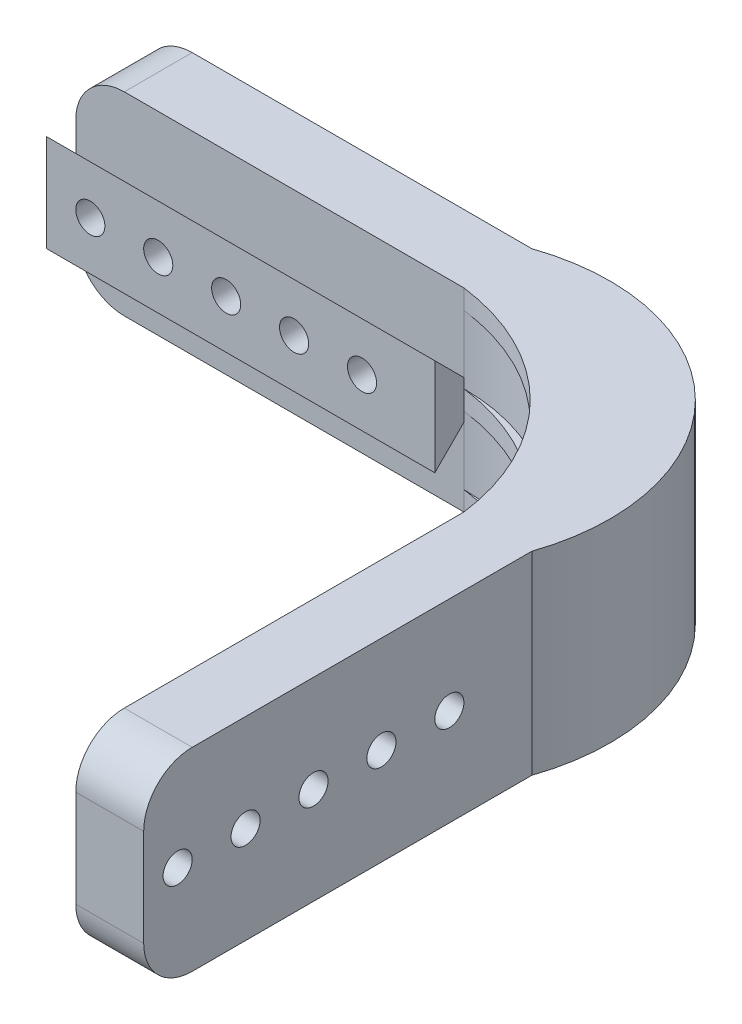
SolidWorks part; units mm, degrees
ref_plane "Front Plane" through (0, 0, 0) normal (0, 0, 1) x (1, 0, 0)
ref_plane "Top Plane" through (0, 0, 0) normal (0, 1, 0) x (1, 0, 0)
ref_plane "Right Plane" through (0, 0, 0) normal (1, 0, 0) x (0, 0, -1)
sketch "Sketch1" plane through (0, 0, 0) normal (0, 1, 0) x (1, 0, 0)
  line L0 (0, 0) -> (40, 0)
  line L1 (67, -27) -> (67, -67)
  line L2 (0, -7) -> (40, -7)
  line L3 (60, -27) -> (60, -67)
  line L4 (60, -67) -> (67, -67)
  line L5 (0, -7) -> (0, 0)
  arc A0 (40, 0) -> (67, -27) centre (40, -27) cw
  arc A1 (40, -7) -> (60, -27) centre (40, -27) cw
  dimension "D4" = 20
  dimension "D2" = 40
  dimension "D3" = 40
  dimension "D1" = 7
extrude "Boss-Extrude1" add sketch "Sketch1" along normal blind 20
sketch "Sketch2" plane through (0, 0, 0) normal (1, 0, 0) x (0, 0, -1)
  line L1 (-7, 20) -> (-7, 0) construction
  line L2 (-10, 15) -> (-10, 5)
  line L3 (-10, 5) -> (-7, 8)
  line L4 (-7, 8) -> (-7, 12)
  line L5 (-7, 10) -> (-10, 10) construction
  line L6 (-7, 12) -> (-10, 15)
  line L7 (-7, 20) -> (-27, 20) construction
  dimension "D1" = 10
  dimension "D2" = 4
  dimension "D3" = 3
  dimension "D9" = 10
extrude "Boss-Extrude2" add sketch "Sketch2" along normal blind 40
ref_plane "Plane1" through (0, 0, 65) normal (0, 0, 1) x (1, 0, 0)
sketch "Sketch3" plane through (0, 0, 65) normal (0, 0, 1) x (1, 0, 0)
  line L6 (67, 12) -> (67, 8)
  line L8 (67, 20) -> (67, 0) construction
  line L9 (67, 8) -> (70, 5)
  line L10 (70, 5) -> (70, 15)
  line L11 (70, 15) -> (67, 12)
  line L12 (67, 10) -> (70, 10) construction
  line L13 (60, 20) -> (67, 20) construction
  dimension "D1" = 10
  dimension "D2" = 4
  dimension "D3" = 3
  dimension "D4" = 10
extrude "Boss-Extrude3" [suppressed] add sketch "Sketch3" against normal blind 40
sketch "Sketch4" plane through (0, 0, 0) normal (1, 0, 0) x (0, 0, -1)
  line L0 (-27, 20) -> (-67, 20) construction
  line L1 (-67, 20) -> (-67, 0) construction
  circle A0 centre (-63.5, 10) radius 1.5
  dimension "D1" = 3
  dimension "D2" = 10
  dimension "D3" = 3.5
extrude "Cut-Extrude1" cut sketch "Sketch4" along normal blind 75
pattern_linear "LPattern1" count 5 spacing 7 along (0, 0, -1) of "Cut-Extrude1"
sketch "Sketch5" plane through (0, 0, 0) normal (0, 0, 1) x (1, 0, 0)
  line L0 (40, 20) -> (0, 20) construction
  line L1 (0, 20) -> (0, 0) construction
  circle A0 centre (4.5, 10) radius 1.5
  dimension "D1" = 3
  dimension "D2" = 10
  dimension "D3" = 4.5
extrude "Cut-Extrude2" cut sketch "Sketch5" along normal blind 14
pattern_linear "LPattern2" count 5 spacing 7 along (1, 0, 0) of "Cut-Extrude2"
fillet "Fillet1" [suppressed] radius 0.5
fillet "Fillet2" radius 5 4 edges at (63.5, 0, 67) (63.5, 20, 67) (0, 0, 3.5) (0, 20, 3.5)
sketch "Sketch6" plane through (0, 0, 0) normal (0, 1, 0) x (1, 0, 0)
  line L6 (60, -27) -> (60, -62)
  line L7 (60, -62) -> (67, -62)
  line L8 (67, -62) -> (67, -27)
  line L9 (40, 0) -> (5, 0)
  line L10 (5, 0) -> (5, -7)
  line L11 (5, -7) -> (40, -7)
  arc A0 (67, -27) -> (40, 0) centre (46.8968, -20.1032) ccw
  arc A3 (67, -27) -> (40, 0) centre (40, -27) ccw
  arc A4 (60, -27) -> (40, -7) centre (40, -27) ccw
  arc A5 (67, -27) -> (40, 0) centre (40, -27) ccw
  dimension "D1" = 0
extrude "Boss-Extrude4" add sketch "Sketch6" along normal up to surface (20 mm away) up to face at (44.2168, 20, 22.7832)
sketch "Sketch8" plane through (0, 0, 0) normal (0, 1, 0) x (1, 0, 0)
  arc A0 (40, -7) -> (60, -27) centre (37.0789, -29.9211) cw
  arc A1 (40, -7) -> (60, -27) centre (40, -27) cw
extrude "Boss-Extrude5" add sketch "Sketch8" along normal blind 2
pattern_linear "LPattern3" count 3 spacing 9 along (0, 1, 0) of "Boss-Extrude5"
